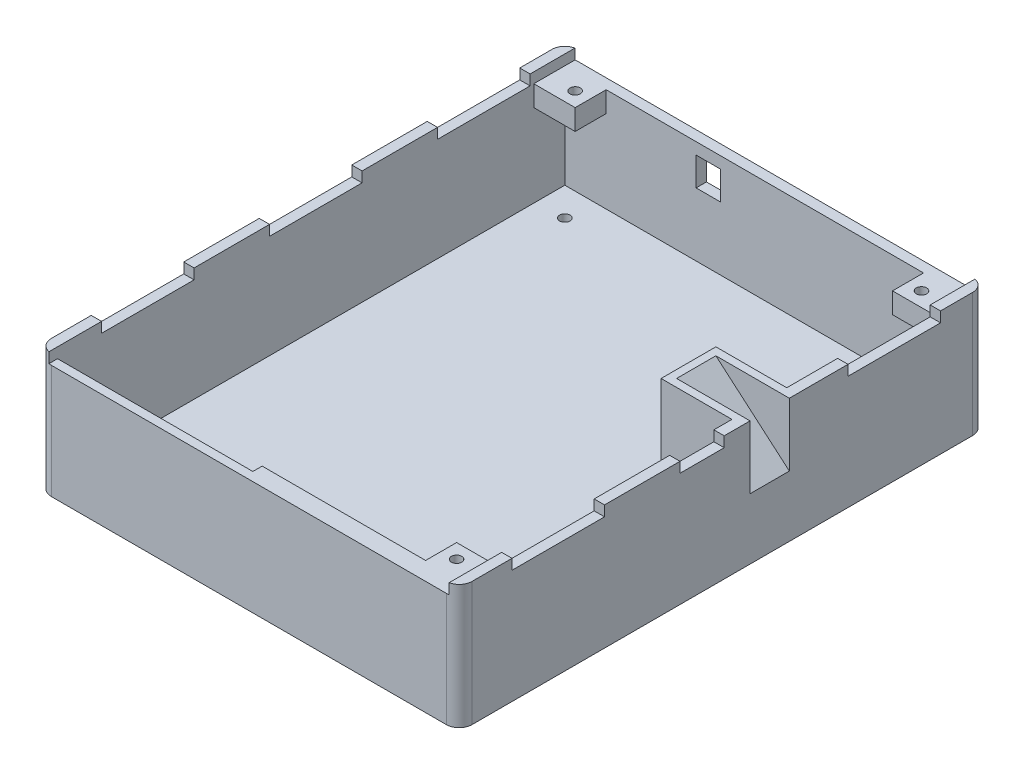
SolidWorks part; units mm, degrees
ref_plane "Front Plane" through (0, 0, 0) normal (0, 0, 1) x (1, 0, 0)
ref_plane "Top Plane" through (0, 0, 0) normal (0, 1, 0) x (1, 0, 0)
ref_plane "Right Plane" through (0, 0, 0) normal (1, 0, 0) x (0, 0, -1)
sketch "Sketch1" plane through (0, 95.465, 0) normal (0, 1, 0) x (1, 0, 0)
  line L9 (159.9807, -123.0664) -> (159.9807, -100.3704) construction
  line L13 (159.9807, -65.3704) -> (159.9807, -47.9349) construction
  line L26 (5.9807, -65.3704) -> (1.9807, -65.3704) construction
  line L27 (1.9807, -65.3704) -> (1.9807, -100.3704) construction
  line L28 (1.9807, -100.3704) -> (5.9807, -100.3704) construction
  line L30 (5.9807, -130.3704) -> (1.9807, -130.3704) construction
  line L31 (1.9807, -130.3704) -> (1.9807, -165.3704) construction
  line L32 (1.9807, -165.3704) -> (5.9807, -165.3704) construction
  line L34 (5.9807, -195.3704) -> (1.9807, -195.3704) construction
  line L35 (1.9807, -195.3704) -> (1.9807, -230.3704) construction
  line L36 (1.9807, -230.3704) -> (5.9807, -230.3704) construction
  line L38 (5.9807, -247.8059) -> (159.9807, -247.8059) construction
  line L39 (159.9807, -247.8059) -> (159.9807, -230.3704) construction
  line L43 (159.9807, -195.3704) -> (159.9807, -165.3704) construction
  line L47 (5.9807, -130.3704) -> (5.9807, -100.3704) construction
  line L48 (5.9807, -195.3704) -> (5.9807, -165.3704) construction
  line L49 (5.9807, -247.8059) -> (5.9807, -230.3704) construction
  line L50 (163.9807, -195.3704) -> (163.9807, -230.3704) construction
  line L51 (163.9807, -149.0664) -> (163.9807, -165.3704) construction
  line L52 (159.9807, -139.0664) -> (159.9807, -149.0664) construction
  line L53 (135.9622, -139.0664) -> (159.9807, -139.0664) construction
  line L54 (135.9622, -123.0664) -> (135.9622, -139.0664) construction
  line L55 (159.9807, -123.0664) -> (135.9622, -123.0664) construction
  line L56 (163.9807, -100.3704) -> (159.9807, -100.3704) construction
  line L57 (159.9807, -65.3704) -> (163.9807, -65.3704) construction
  line L58 (163.9807, -65.3704) -> (163.9807, -100.3704) construction
  line L59 (130.9016, -47.9349) -> (159.9807, -47.9349) construction
  line L60 (5.9807, -47.9349) -> (118.5112, -47.9349) construction
  line L61 (5.9807, -65.3704) -> (5.9807, -47.9349) construction
  line L62 (5.9807, -130.3704) -> (1.9807, -130.3704)
  line L63 (5.9807, -130.3704) -> (5.9807, -100.3704)
  line L64 (1.9807, -100.3704) -> (5.9807, -100.3704)
  line L65 (1.9807, -130.3704) -> (1.9807, -165.3704)
  line L66 (1.9807, -165.3704) -> (5.9807, -165.3704)
  line L67 (5.9807, -195.3704) -> (5.9807, -165.3704)
  line L68 (5.9807, -195.3704) -> (1.9807, -195.3704)
  line L69 (1.9807, -195.3704) -> (1.9807, -230.3704)
  line L70 (1.9807, -230.3704) -> (5.9807, -230.3704)
  line L71 (5.9807, -247.8059) -> (5.9807, -230.3704)
  line L72 (5.9807, -247.8059) -> (159.9807, -247.8059)
  line L73 (159.9807, -247.8059) -> (159.9807, -230.3704)
  line L74 (163.9807, -195.3704) -> (163.9807, -230.3704)
  line L75 (159.9807, -195.3704) -> (159.9807, -165.3704)
  line L76 (163.9807, -149.0664) -> (163.9807, -165.3704)
  line L77 (159.9807, -139.0664) -> (159.9807, -149.0664)
  line L78 (135.9622, -139.0664) -> (159.9807, -139.0664)
  line L79 (135.9622, -123.0664) -> (135.9622, -139.0664)
  line L80 (159.9807, -123.0664) -> (135.9622, -123.0664)
  line L81 (159.9807, -123.0664) -> (159.9807, -100.3704)
  line L82 (163.9807, -100.3704) -> (159.9807, -100.3704)
  line L83 (159.9807, -65.3704) -> (163.9807, -65.3704)
  line L84 (163.9807, -65.3704) -> (163.9807, -100.3704)
  line L85 (159.9807, -65.3704) -> (159.9807, -47.9349)
  line L86 (130.9016, -47.9349) -> (159.9807, -47.9349)
  line L87 (5.9807, -47.9349) -> (118.5112, -47.9349)
  line L88 (5.9807, -65.3704) -> (5.9807, -47.9349)
  line L89 (5.9807, -65.3704) -> (1.9807, -65.3704)
  line L90 (1.9807, -65.3704) -> (1.9807, -100.3704)
  line L91 (163.9807, -230.3704) -> (159.9807, -230.3704) construction
  line L92 (159.9807, -195.3704) -> (163.9807, -195.3704) construction
  line L93 (163.9807, -230.3704) -> (159.9807, -230.3704)
  line L94 (159.9807, -195.3704) -> (163.9807, -195.3704)
  line L95 (163.9807, -165.3704) -> (159.9807, -165.3704) construction
  line L96 (163.9807, -165.3704) -> (159.9807, -165.3704)
  line L97 (159.9807, -149.0664) -> (163.9807, -149.0664) construction
  line L98 (159.9807, -149.0664) -> (163.9807, -149.0664)
  line L99 (5.5807, -47.5349) -> (118.5112, -47.5349)
  line L100 (5.5807, -64.9704) -> (5.5807, -47.5349)
  line L101 (5.5807, -64.9704) -> (1.5807, -64.9704)
  line L102 (1.5807, -64.9704) -> (1.5807, -100.7704)
  line L103 (1.5807, -100.7704) -> (5.5807, -100.7704)
  line L104 (5.5807, -129.9704) -> (5.5807, -100.7704)
  line L105 (5.5807, -129.9704) -> (1.5807, -129.9704)
  line L106 (1.5807, -129.9704) -> (1.5807, -165.7704)
  line L107 (1.5807, -165.7704) -> (5.5807, -165.7704)
  line L108 (5.5807, -194.9704) -> (5.5807, -165.7704)
  line L109 (5.5807, -194.9704) -> (1.5807, -194.9704)
  line L110 (1.5807, -194.9704) -> (1.5807, -230.7704)
  line L111 (1.5807, -230.7704) -> (5.5807, -230.7704)
  line L112 (5.5807, -248.2059) -> (5.5807, -230.7704)
  line L113 (5.5807, -248.2059) -> (160.3807, -248.2059)
  line L114 (160.3807, -248.2059) -> (160.3807, -230.7704)
  line L115 (164.3807, -230.7704) -> (160.3807, -230.7704)
  line L116 (164.3807, -194.9704) -> (164.3807, -230.7704)
  line L117 (160.3807, -194.9704) -> (164.3807, -194.9704)
  line L118 (160.3807, -194.9704) -> (160.3807, -165.7704)
  line L119 (164.3807, -165.7704) -> (160.3807, -165.7704)
  line L120 (164.3807, -148.6664) -> (164.3807, -165.7704)
  line L121 (160.3807, -148.6664) -> (164.3807, -148.6664)
  line L122 (160.3807, -138.6664) -> (160.3807, -148.6664)
  line L123 (136.3622, -138.6664) -> (160.3807, -138.6664)
  line L124 (136.3622, -123.4664) -> (136.3622, -138.6664)
  line L125 (160.3807, -123.4664) -> (136.3622, -123.4664)
  line L126 (160.3807, -123.4664) -> (160.3807, -100.7704)
  line L127 (164.3807, -100.7704) -> (160.3807, -100.7704)
  line L128 (164.3807, -64.9704) -> (164.3807, -100.7704)
  line L129 (160.3807, -64.9704) -> (164.3807, -64.9704)
  line L130 (160.3807, -64.9704) -> (160.3807, -47.5349)
  line L131 (130.9016, -47.5349) -> (160.3807, -47.5349)
  line L133 (164.3807, -248.2059) -> (1.5807, -248.2059)
  line L134 (164.3807, -248.2059) -> (164.3807, -47.5349)
  line L135 (164.3807, -47.5349) -> (1.5807, -47.5349)
  line L136 (1.5807, -248.2059) -> (1.5807, -47.5349)
  dimension "D1" = 0.4
extrude "Boss-Extrude2" add sketch "Sketch1" against normal blind 4 contours L136 L101 L100 L135 | L136 L105 L104 L103 | L136 L109 L108 L107 | L136 L133 L112 L111 | L133 L134 L115 L114 | L117 L134 L119 L118 | L121 L134 L127 L126 L125 L124 L123 L122 | L134 L135 L130 L129 region at (3.5807, 95.465, 56.2527) region at (162.3807, 95.465, 56.2527) region at (3.5807, 95.465, 115.3704) region at (3.5807, 95.465, 180.3704) region at (153.1929, 95.465, 128.8817) region at (3.5807, 95.465, 239.4882) region at (162.3807, 95.465, 180.3704) region at (162.3807, 95.465, 239.4882)
sketch "Sketch2" plane through (0, 95.465, 0) normal (0, 1, 0) x (1, 0, 0)
  line L1 (136.3622, -123.4664) -> (164.3807, -123.4664)
  line L2 (136.3622, -123.4664) -> (136.3622, -138.6664)
  line L3 (136.3622, -138.6664) -> (164.3807, -138.6664)
  line L4 (164.3807, -123.4664) -> (164.3807, -138.6664)
  line L8 (160.3807, -148.6664) -> (164.3807, -148.6664)
  line L9 (164.3807, -148.6664) -> (164.3807, -100.7704)
  line L10 (164.3807, -100.7704) -> (160.3807, -100.7704)
  line L11 (160.3807, -100.7704) -> (160.3807, -123.4664)
  line L12 (160.3807, -123.4664) -> (136.3622, -123.4664)
  line L13 (136.3622, -123.4664) -> (136.3622, -138.6664)
  line L14 (136.3622, -138.6664) -> (160.3807, -138.6664)
  line L15 (160.3807, -138.6664) -> (160.3807, -148.6664)
  line L16 (160.3807, -148.6664) -> (164.3807, -148.6664)
  line L17 (164.3807, -148.6664) -> (164.3807, -100.7704)
  line L18 (164.3807, -100.7704) -> (160.3807, -100.7704)
  line L19 (160.3807, -100.7704) -> (160.3807, -123.4664)
  line L20 (160.3807, -123.4664) -> (136.3622, -123.4664)
  line L21 (136.3622, -123.4664) -> (136.3622, -138.6664)
  line L22 (136.3622, -138.6664) -> (160.3807, -138.6664)
  line L23 (160.3807, -138.6664) -> (160.3807, -148.6664)
  line M10 (164.3807, -148.6664) -> (164.3807, -100.7704)
  line M13 (160.3807, -123.4664) -> (136.3622, -123.4664)
  line M14 (136.3622, -123.4664) -> (136.3622, -138.6664)
  line M15 (136.3622, -138.6664) -> (160.3807, -138.6664)
  dimension "D1" = 0
extrude "Cut-Extrude1" cut sketch "Sketch2" against normal blind 4 contours L3 L1 M15 M10 M13 M14 region at (150.3715, 95.465, 131.0664)
sketch "Sketch3" plane through (0, 91.465, 0) normal (0, -1, 0) x (1, 0, 0)
  line L0 (160.3807, 51.5349) -> (160.3807, 244.2059)
  line L1 (164.3807, 47.5349) -> (1.5807, 47.5349)
  line L2 (164.3807, 47.5349) -> (164.3807, 248.2059)
  line L3 (164.3807, 248.2059) -> (1.5807, 248.2059)
  line L4 (1.5807, 47.5349) -> (1.5807, 248.2059)
  line L5 (160.3807, 244.2059) -> (5.5807, 244.2059)
  line L6 (5.5807, 51.5349) -> (5.5807, 244.2059)
  line L7 (160.3807, 51.5349) -> (5.5807, 51.5349)
  dimension "D1" = 4
extrude "Boss-Extrude3" add sketch "Sketch3" along normal blind 40
sketch "Sketch4" plane through (0, 51.465, 0) normal (0, -1, 0) x (1, 0, 0)
  line L1 (1.5807, 47.5349) -> (164.3807, 47.5349)
  line L2 (1.5807, 47.5349) -> (1.5807, 248.2059)
  line L3 (1.5807, 248.2059) -> (164.3807, 248.2059)
  line L4 (164.3807, 47.5349) -> (164.3807, 248.2059)
extrude "Boss-Extrude4" add sketch "Sketch4" along normal blind 4
fillet "Fillet1" radius 5 1 edges at (1.5807, 71.465, 248.2059)
fillet "Fillet2" radius 5 1 edges at (164.3807, 71.465, 248.2059)
fillet "Fillet3" radius 5 1 edges at (164.3807, 71.465, 47.5349)
fillet "Fillet4" radius 5 1 edges at (1.5807, 71.465, 47.5349)
sketch "Sketch5" plane through (0, 47.465, 0) normal (0, -1, 0) x (1, 0, 0)
  line L0 (164.3807, 52.5349) -> (164.3807, 243.2059) construction
  line L1 (164.3807, 47.5349) -> (149.3807, 47.5349)
  line L2 (164.3807, 47.5349) -> (164.3807, 62.5349)
  line L3 (164.3807, 62.5349) -> (149.3807, 62.5349)
  line L4 (1.5807, 243.2059) -> (1.5807, 52.5349)
  line L5 (6.5807, 47.5349) -> (159.3807, 47.5349)
  line L6 (164.3807, 52.5349) -> (164.3807, 243.2059)
  line L7 (159.3807, 248.2059) -> (6.5807, 248.2059)
  line L8 (1.5807, 243.2059) -> (1.5807, 52.5349)
  line L9 (6.5807, 47.5349) -> (159.3807, 47.5349)
  line L10 (164.3807, 52.5349) -> (164.3807, 243.2059)
  line L11 (159.3807, 248.2059) -> (6.5807, 248.2059)
  line L12 (149.3807, 47.5349) -> (149.3807, 62.5349)
  line L13 (1.5807, 47.5349) -> (16.5807, 47.5349)
  line L14 (1.5807, 47.5349) -> (1.5807, 62.5349)
  line L15 (1.5807, 62.5349) -> (16.5807, 62.5349)
  line L16 (16.5807, 47.5349) -> (16.5807, 62.5349)
  line L17 (1.5807, 248.2059) -> (16.5807, 248.2059)
  line L18 (1.5807, 248.2059) -> (1.5807, 233.2059)
  line L19 (1.5807, 233.2059) -> (16.5807, 233.2059)
  line L20 (16.5807, 248.2059) -> (16.5807, 233.2059)
  line L21 (164.3807, 248.2059) -> (149.3807, 248.2059)
  line L22 (164.3807, 248.2059) -> (164.3807, 233.2059)
  line L23 (164.3807, 233.2059) -> (149.3807, 233.2059)
  line L24 (149.3807, 248.2059) -> (149.3807, 233.2059)
  line L25 (6.5807, 47.5349) -> (159.3807, 47.5349) construction
  line L26 (1.5807, 243.2059) -> (1.5807, 52.5349) construction
  line L27 (159.3807, 248.2059) -> (6.5807, 248.2059) construction
  circle A0 centre (149.3807, 62.5349) radius 2
  circle A1 centre (16.5807, 62.5349) radius 2
  circle A2 centre (149.3807, 233.2059) radius 2
  circle A3 centre (16.5807, 233.2059) radius 2
  arc A4 (1.5807, 52.5349) -> (6.5807, 47.5349) centre (6.5807, 52.5349) ccw
  arc A5 (159.3807, 47.5349) -> (164.3807, 52.5349) centre (159.3807, 52.5349) ccw
  arc A8 (1.5807, 52.5349) -> (6.5807, 47.5349) centre (6.5807, 52.5349) ccw
  arc A9 (159.3807, 47.5349) -> (164.3807, 52.5349) centre (159.3807, 52.5349) ccw
  arc A12 (164.3807, 243.2059) -> (159.3807, 248.2059) centre (159.3807, 243.2059) ccw
  arc A13 (164.3807, 243.2059) -> (159.3807, 248.2059) centre (159.3807, 243.2059) ccw
  arc A14 (6.5807, 248.2059) -> (1.5807, 243.2059) centre (6.5807, 243.2059) ccw
  arc A15 (6.5807, 248.2059) -> (1.5807, 243.2059) centre (6.5807, 243.2059) ccw
  dimension "D10" = 4
  dimension "D11" = 4
  dimension "D12" = 4
  dimension "D13" = 4
  dimension "D2" = 15
  dimension "D3" = 15
  dimension "D4" = 15
  dimension "D5" = 15
  dimension "D6" = 15
  dimension "D7" = 15
  dimension "D8" = 15
  dimension "D9" = 15
  dimension "D1" = 0
extrude "Cut-Extrude2" cut sketch "Sketch5" against normal up to surface (4 mm away) contours A0 | A1 | A3 | A2 up to face at (82.9807, 51.465, 147.8704)
sketch "Sketch6" plane through (0, 91.465, 0) normal (0, 1, 0) x (1, 0, 0)
  line L0 (6.5807, -47.5349) -> (5.5807, -47.5349)
  line L1 (5.5807, -47.636) -> (5.5807, -47.5349)
  line L3 (5.5807, -47.5349) -> (21.5807, -47.5349)
  line L4 (5.5807, -47.5349) -> (5.5807, -63.5349)
  line L5 (5.5807, -63.5349) -> (21.5807, -63.5349)
  line L6 (159.3807, -47.5349) -> (6.5807, -47.5349)
  line L7 (5.5807, -47.636) -> (5.5807, -51.5349)
  line L8 (5.5807, -51.5349) -> (160.3807, -51.5349)
  line L9 (160.3807, -51.5349) -> (160.3807, -47.636)
  line L10 (159.3807, -47.5349) -> (6.5807, -47.5349)
  line L11 (5.5807, -47.636) -> (5.5807, -51.5349)
  line L12 (5.5807, -51.5349) -> (160.3807, -51.5349)
  line L13 (160.3807, -51.5349) -> (160.3807, -47.636)
  line L14 (21.5807, -47.5349) -> (21.5807, -63.5349)
  arc A2 (6.5807, -47.5349) -> (5.5807, -47.636) centre (6.5807, -52.5349) ccw
  arc A3 (160.3807, -47.636) -> (159.3807, -47.5349) centre (159.3807, -52.5349) ccw
  arc A4 (6.5807, -47.5349) -> (5.5807, -47.636) centre (6.5807, -52.5349) ccw
  arc A5 (160.3807, -47.636) -> (159.3807, -47.5349) centre (159.3807, -52.5349) ccw
  line M14 (5.5807, -51.5349) -> (160.3807, -51.5349)
  dimension "D2" = 16
  dimension "D3" = 16
  dimension "D1" = 0
extrude "Boss-Extrude5" add sketch "Sketch6" against normal blind 8 contours L14 L4 L5 M14 region at (13.5807, 91.465, 57.5349)
sketch "Sketch7" plane through (0, 91.465, 0) normal (0, 1, 0) x (1, 0, 0)
  circle A0 centre (15.9807, -57.9349) radius 2
extrude "Cut-Extrude3" cut sketch "Sketch7" against normal blind 8
ref_plane "Plane1" through (82.9807, 0, 0) normal (-1, 0, 0) x (0, 0, 1)
mirror "Mirror1" about plane through (82.9807, 0, 0) normal (-1, 0, 0) of "Cut-Extrude3", "Boss-Extrude5"
sketch "Sketch8" plane through (0, 91.465, 0) normal (0, 1, 0) x (1, 0, 0)
  line L0 (159.3807, -248.2059) -> (160.3807, -248.2059)
  line L1 (160.3807, -248.2059) -> (160.3807, -248.1049)
  line L3 (160.3807, -248.2059) -> (144.3807, -248.2059)
  line L4 (6.5807, -248.2059) -> (159.3807, -248.2059)
  line L5 (160.3807, -248.1049) -> (160.3807, -244.2059)
  line L6 (160.3807, -244.2059) -> (5.5807, -244.2059)
  line L7 (5.5807, -244.2059) -> (5.5807, -248.1049)
  line L8 (6.5807, -248.2059) -> (159.3807, -248.2059)
  line L9 (160.3807, -248.1049) -> (160.3807, -244.2059)
  line L10 (160.3807, -244.2059) -> (5.5807, -244.2059)
  line L11 (5.5807, -244.2059) -> (5.5807, -248.1049)
  line L12 (160.3807, -248.2059) -> (160.3807, -232.2059)
  line L13 (160.3807, -232.2059) -> (144.3807, -232.2059)
  line L14 (144.3807, -248.2059) -> (144.3807, -232.2059)
  arc A2 (159.3807, -248.2059) -> (160.3807, -248.1049) centre (159.3807, -243.2059) ccw
  arc A3 (159.3807, -248.2059) -> (160.3807, -248.1049) centre (159.3807, -243.2059) ccw
  arc A4 (5.5807, -248.1049) -> (6.5807, -248.2059) centre (6.5807, -243.2059) ccw
  arc A5 (5.5807, -248.1049) -> (6.5807, -248.2059) centre (6.5807, -243.2059) ccw
  line M13 (160.3807, -244.2059) -> (5.5807, -244.2059)
  dimension "D2" = 16
  dimension "D3" = 16
  dimension "D1" = 0
extrude "Boss-Extrude6" add sketch "Sketch8" against normal blind 8 contours L14 L12 L13 M13 region at (152.3807, 91.465, 238.2059)
sketch "Sketch9" plane through (0, 91.465, 0) normal (0, 1, 0) x (1, 0, 0)
  circle A0 centre (149.9807, -237.8059) radius 2
extrude "Cut-Extrude4" cut sketch "Sketch9" against normal blind 8
sketch "Sketch11" plane through (0, 91.465, 0) normal (0, 1, 0) x (1, 0, 0)
  circle A0 centre (11.1807, -243.8759) radius 2
  circle A1 centre (74.6807, -243.8759) radius 2
  dimension "D1" = 4
  dimension "D2" = 4
extrude "Cut-Extrude5" cut sketch "Sketch11" against normal blind 8
sketch "Sketch12" plane through (164.3807, 0, 0) normal (1, 0, 0) x (0, 0, -1)
  line L1 (-123.4664, 95.465) -> (-138.6664, 95.465)
  line L2 (-123.4664, 95.465) -> (-123.4664, 91.465)
  line L3 (-123.4664, 91.465) -> (-138.6664, 91.465)
  line L4 (-138.6664, 95.465) -> (-138.6664, 91.465)
  line L6 (-123.4664, 91.465) -> (-123.4664, 71.045)
  line L7 (-123.4664, 71.045) -> (-138.6664, 71.045)
  line L8 (-138.6664, 91.465) -> (-138.6664, 71.045)
  line M11 (-123.4664, 91.465) -> (-138.6664, 91.465)
  dimension "D1" = 24.42
extrude "Cut-Extrude6" cut sketch "Sketch12" against normal up to surface (4 mm away) contours L8 L7 L6 M11 region at (164.3807, 81.255, 131.0664) up to face at (160.3807, 88.8935, 146.8053)
sketch "Sketch13" plane through (0, 51.465, 0) normal (0, 1, 0) x (1, 0, 0)
  line L0 (160.3807, -123.4664) -> (160.3807, -138.6664) construction
  line L1 (160.3807, -123.4664) -> (160.3807, -138.6664)
  line L2 (160.3807, -120.4664) -> (132.9607, -120.4664)
  line L3 (160.3807, -123.4664) -> (135.9607, -123.4664)
  line L4 (160.3807, -51.5349) -> (5.5807, -51.5349)
  line L5 (5.5807, -51.5349) -> (5.5807, -244.2059)
  line L6 (5.5807, -244.2059) -> (160.3807, -244.2059)
  line L7 (160.3807, -244.2059) -> (160.3807, -51.5349)
  line L8 (160.3807, -51.5349) -> (5.5807, -51.5349)
  line L9 (5.5807, -51.5349) -> (5.5807, -244.2059)
  line L10 (5.5807, -244.2059) -> (160.3807, -244.2059)
  line L11 (160.3807, -244.2059) -> (160.3807, -51.5349)
  line L12 (160.3807, -123.4664) -> (160.3807, -138.6664)
  line L13 (160.3807, -138.6664) -> (135.9607, -138.6664)
  line L14 (135.9607, -123.4664) -> (135.9607, -138.6664)
  line L15 (132.9607, -120.4664) -> (132.9607, -141.6664)
  line L16 (160.3807, -141.6664) -> (132.9607, -141.6664)
  line M16 (160.3807, -244.2059) -> (160.3807, -51.5349)
  dimension "D2" = 24.42
  dimension "D1" = 0
  dimension "D3" = 3
extrude "Boss-Extrude7" add sketch "Sketch13" along normal up to surface (44 mm away) contours L16 L11 L13 L14 L3 L2 L15 M16 region at (148.1707, 51.465, 123.1198) up to face at (162.3807, 95.465, 112.1184)
sketch "Sketch14" plane through (0, 51.465, 0) normal (0, 1, 0) x (1, 0, 0)
  line L4 (135.9607, -123.4664) -> (135.9607, -138.6664)
  line L5 (135.9607, -138.6664) -> (160.3807, -138.6664)
  line L6 (160.3807, -138.6664) -> (160.3807, -123.4664)
  line L7 (160.3807, -123.4664) -> (135.9607, -123.4664)
  line L8 (135.9607, -123.4664) -> (135.9607, -138.6664)
  line L9 (135.9607, -138.6664) -> (160.3807, -138.6664)
  line L10 (160.3807, -138.6664) -> (160.3807, -123.4664)
  line L11 (160.3807, -123.4664) -> (135.9607, -123.4664)
  dimension "D1" = 0
extrude "Boss-Extrude8" add sketch "Sketch14" along normal up to surface (19.58 mm away) up to face at (162.3807, 71.045, 131.0664)
chamfer "Chamfer2" distance 24.42 distance2 28.42 1 edges at (135.9607, 71.045, 131.0664) first distance on face at (135.9607, 83.255, 131.0664)
sketch "Sketch15" plane through (0, 0, 47.5349) normal (0, 0, -1) x (-1, 0, 0)
  line L0 (-21.5807, 83.465) -> (-21.5807, 91.465) construction
  line L1 (-21.5807, 86.965) -> (-21.5807, 91.465)
  line L2 (-21.5807, 86.965) -> (-50.1407, 86.965)
  line L3 (-50.1407, 86.965) -> (-61.0607, 86.965)
  line L4 (-21.5807, 91.465) -> (-21.5807, 86.965)
  line L5 (-56.3857, 86.965) -> (-65.7357, 86.965)
  line L7 (-65.7357, 86.965) -> (-56.3857, 86.965)
  line L8 (-65.7357, 86.965) -> (-65.7357, 75.965)
  line L9 (-65.7357, 75.965) -> (-56.3857, 75.965)
  line L10 (-56.3857, 86.965) -> (-56.3857, 75.965)
  point P10 (-61.0607, 86.965)
  dimension "D1" = 28.56
  dimension "D2" = 10.92
  dimension "D3" = 4.5
  dimension "D4" = 9.35
  dimension "D5" = 11
extrude "Cut-Extrude7" cut sketch "Sketch15" against normal blind 10 contours L10 L3 L5 L8 L9 region at (61.0607, 81.465, 47.5349)
sketch "Sketch16" plane through (0, 0, 248.2059) normal (0, 0, 1) x (1, 0, 0)
  line L4 (6.5807, 47.465) -> (159.3807, 47.465)
  line L5 (159.3807, 47.465) -> (159.3807, 91.465)
  line L6 (159.3807, 91.465) -> (6.5807, 91.465)
  line L7 (6.5807, 91.465) -> (6.5807, 47.465)
  line L8 (6.5807, 47.465) -> (159.3807, 47.465)
  line L9 (159.3807, 47.465) -> (159.3807, 91.465)
  line L10 (159.3807, 91.465) -> (6.5807, 91.465)
  line L11 (6.5807, 91.465) -> (6.5807, 47.465)
  line L14 (1.5807, 47.465) -> (6.5807, 47.465)
  line L15 (6.5807, 47.465) -> (6.5807, 91.465)
  line L16 (6.5807, 91.465) -> (5.5807, 91.465)
  line L17 (5.5807, 91.465) -> (5.5807, 95.465)
  line L18 (5.5807, 95.465) -> (1.5807, 95.465)
  line L19 (1.5807, 95.465) -> (1.5807, 47.465)
  line L20 (1.5807, 47.465) -> (6.5807, 47.465)
  line L21 (6.5807, 47.465) -> (6.5807, 91.465)
  line L22 (6.5807, 91.465) -> (5.5807, 91.465)
  line L23 (5.5807, 91.465) -> (5.5807, 95.465)
  line L24 (5.5807, 95.465) -> (1.5807, 95.465)
  line L25 (1.5807, 95.465) -> (1.5807, 47.465)
  line L26 (159.3807, 47.465) -> (164.3807, 47.465)
  line L27 (164.3807, 47.465) -> (164.3807, 95.465)
  line L28 (164.3807, 95.465) -> (160.3807, 95.465)
  line L29 (160.3807, 95.465) -> (160.3807, 91.465)
  line L30 (160.3807, 91.465) -> (159.3807, 91.465)
  line L31 (159.3807, 91.465) -> (159.3807, 47.465)
  line L32 (159.3807, 47.465) -> (164.3807, 47.465)
  line L33 (164.3807, 47.465) -> (164.3807, 95.465)
  line L34 (164.3807, 95.465) -> (160.3807, 95.465)
  line L35 (160.3807, 95.465) -> (160.3807, 91.465)
  line L36 (160.3807, 91.465) -> (159.3807, 91.465)
  line L37 (159.3807, 91.465) -> (159.3807, 47.465)
  line M17 (6.5807, 47.465) -> (159.3807, 47.465)
  line M18 (159.3807, 47.465) -> (159.3807, 91.465)
  line M19 (159.3807, 91.465) -> (6.5807, 91.465)
  line M20 (6.5807, 91.465) -> (6.5807, 47.465)
  dimension "D1" = 0
  dimension "D2" = 0
  dimension "D3" = 0
extrude "Boss-Extrude9" add sketch "Sketch16" along normal blind 3 contours L24 L25 L20 L22 L23 M20 | M20 M17 M18 M19 | L35 L36 L32 L33 L34 M18 region at (82.9807, 69.465, 248.2059) region at (4.0468, 71.0921, 248.2059) region at (161.9146, 71.0921, 248.2059)
sketch "Sketch17" plane through (0, 0, 248.2059) normal (0, 0, -1) x (-1, 0, 0)
  line L6 (-5.5807, 91.465) -> (-6.5807, 91.465)
  line L7 (-6.5807, 91.465) -> (-6.5807, 47.465)
  line L8 (-6.5807, 47.465) -> (-1.5807, 47.465)
  line L9 (-1.5807, 47.465) -> (-1.5807, 95.465)
  line L10 (-1.5807, 95.465) -> (-5.5807, 95.465)
  line L11 (-5.5807, 95.465) -> (-5.5807, 91.465)
  line L12 (-5.5807, 91.465) -> (-6.5807, 91.465)
  line L13 (-6.5807, 91.465) -> (-6.5807, 47.465)
  line L14 (-6.5807, 47.465) -> (-1.5807, 47.465)
  line L15 (-1.5807, 47.465) -> (-1.5807, 95.465)
  line L16 (-1.5807, 95.465) -> (-5.5807, 95.465)
  line L17 (-5.5807, 95.465) -> (-5.5807, 91.465)
  line L18 (-159.3807, 47.465) -> (-159.3807, 91.465)
  line L19 (-159.3807, 91.465) -> (-160.3807, 91.465)
  line L20 (-160.3807, 91.465) -> (-160.3807, 95.465)
  line L21 (-160.3807, 95.465) -> (-164.3807, 95.465)
  line L22 (-164.3807, 95.465) -> (-164.3807, 47.465)
  line L23 (-164.3807, 47.465) -> (-159.3807, 47.465)
  line L24 (-159.3807, 47.465) -> (-159.3807, 91.465)
  line L25 (-159.3807, 91.465) -> (-160.3807, 91.465)
  line L26 (-160.3807, 91.465) -> (-160.3807, 95.465)
  line L27 (-160.3807, 95.465) -> (-164.3807, 95.465)
  line L28 (-164.3807, 95.465) -> (-164.3807, 47.465)
  line L29 (-164.3807, 47.465) -> (-159.3807, 47.465)
  dimension "D1" = 0
  dimension "D2" = 0
extrude "Boss-Extrude10" add sketch "Sketch17" along normal up to vertex (5 mm away) up to point (1.5807, 47.465, 243.2059)
sketch "Sketch18" plane through (0, 91.465, 0) normal (0, 1, 0) x (1, 0, 0)
  line L1 (5.5807, -243.2059) -> (81.1488, -243.2059)
  line L2 (5.5807, -243.2059) -> (5.5807, -247.8059)
  line L3 (5.5807, -247.8059) -> (81.1488, -247.8059)
  line L4 (81.1488, -243.2059) -> (81.1488, -247.8059)
extrude "Cut-Extrude8" cut sketch "Sketch18" against normal up to surface (40 mm away) up to face at (16.5807, 51.465, 64.5349)
fillet "Fillet5" radius 5 2 edges at (164.3807, 71.465, 251.2059) (1.5807, 71.465, 251.2059)
